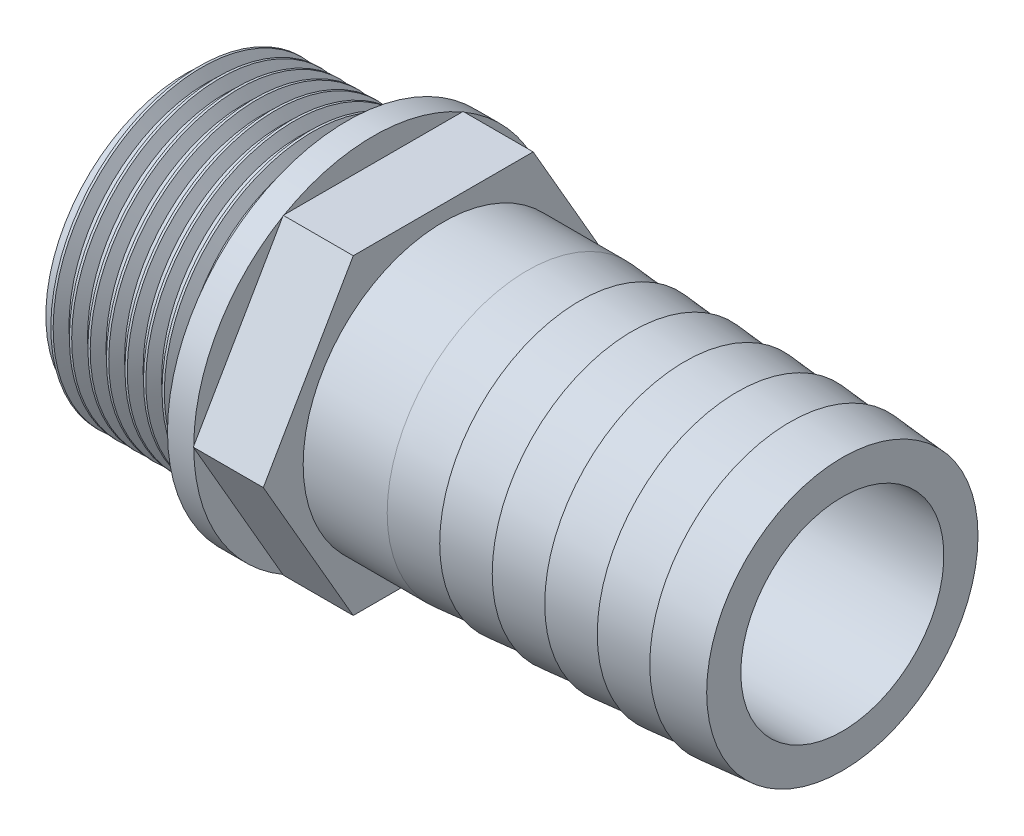
SolidWorks part; units mm, degrees
ref_plane "Płaszczyzna przednia" through (0, 0, 0) normal (0, 0, 1) x (1, 0, 0)
ref_plane "Płaszczyzna górna" through (0, 0, 0) normal (0, 1, 0) x (1, 0, 0)
ref_plane "Płaszczyzna prawa" through (0, 0, 0) normal (1, 0, 0) x (0, 0, -1)
sketch "Szkic1" plane through (0, 0, 0) normal (0, 0, 1) x (1, 0, 0)
  line L0 (0, 16) -> (9, 16)
  line L1 (9, 16) -> (15, 15.5)
  line L2 (15, 15.5) -> (15, 16)
  line L3 (0, 0) -> (54.0342, 0) construction
  line L4 (15, 16) -> (21, 15.5)
  line L5 (21, 15.5) -> (21, 16)
  line L6 (21, 16) -> (27, 15.5)
  line L7 (27, 15.5) -> (27, 16)
  line L8 (27, 16) -> (33, 15.5)
  line L9 (33, 15.5) -> (33, 16)
  line L10 (33, 16) -> (39, 15.5)
  line L11 (39, 15.5) -> (39, 16)
  line L12 (39, 16) -> (45, 15.5)
  line L13 (45, 15.5) -> (45, 11.6)
  line L14 (45, 15.5) -> (45, 16) [skipped]
  line L15 (45, 11.6) -> (-30, 11.6)
  line L16 (-30, 11.6) -> (-30, 16)
  line L17 (-30, 16) -> (-11.6, 16)
  line L18 (-11.6, 16) -> (-11.6, 20.5)
  line L19 (-11.6, 20.5) -> (-8.6, 20.5)
  line L20 (-8.6, 20.5) -> (-8.6, 16)
  line L21 (-8.6, 16) -> (0, 16)
  dimension "D1" = 16
  dimension "D2" = 9
  dimension "D3" = 6
  dimension "D4" = 15.5
  dimension "D6" = 11.6
  dimension "D7" = 20.5
  dimension "D8" = 3
  dimension "D9" = 18.4
  dimension "D10" = 75
  dimension "D5" = 6
revolve "Obrót1" add sketch "Szkic1" angle 360 about L3
sketch "Szkic2" plane through (-8.6, 0, 0) normal (1, 0, 0) x (0, 0, -1)
  line L1 (20.5537, 0) -> (10.2768, 17.8)
  line L2 (10.2768, 17.8) -> (-10.2768, 17.8)
  line L3 (-10.2768, 17.8) -> (-20.5537, 0)
  line L4 (-20.5537, 0) -> (-10.2768, -17.8)
  line L5 (-10.2768, -17.8) -> (10.2768, -17.8)
  line L6 (10.2768, -17.8) -> (20.5537, 0)
  circle A0 centre (0, 0) radius 16
  circle A1 centre (0, 0) radius 17.8 construction
  point P3 (0, 0)
  dimension "D1" = 32
  dimension "D2" = 35.6
extrude "Dodanie-wyciągnięcie1" add sketch "Szkic2" along normal blind 8
thread "Gwint1" pitch 2.1167 method extrude profile "Profil gwintu1" start angle 0, offset 0, length 0, pitch 2.1167, diameter 32
ref_plane "Płaszczyzna1" through (-30, 0, -16) normal (0, -1, 0) x (0, 0, -1)
sketch "Profil gwintu1" plane through (-30, 0, -16) normal (0, -1, 0) x (0, 0, -1)
  line L0 (0, 0) -> (0, 2.1167) construction
  line L1 (0, 0) -> (1.1457, 0.6615)
  line L2 (1.1457, 0.6615) -> (1.1457, 0.926)
  line L3 (1.1457, 0.926) -> (0, 1.5875)
  line L4 (1.1457, 0.7937) -> (0, 0.7937) construction
  line L11 (0, 0) -> (0, 1.5875)
  point P2 (0, 0)
  dimension "Pitch" = 2.1167
  dimension "Profile_Angle" = 60
  dimension "Profile_Land" = 0.2646
  dimension "Profile_Height" = 1.1457
